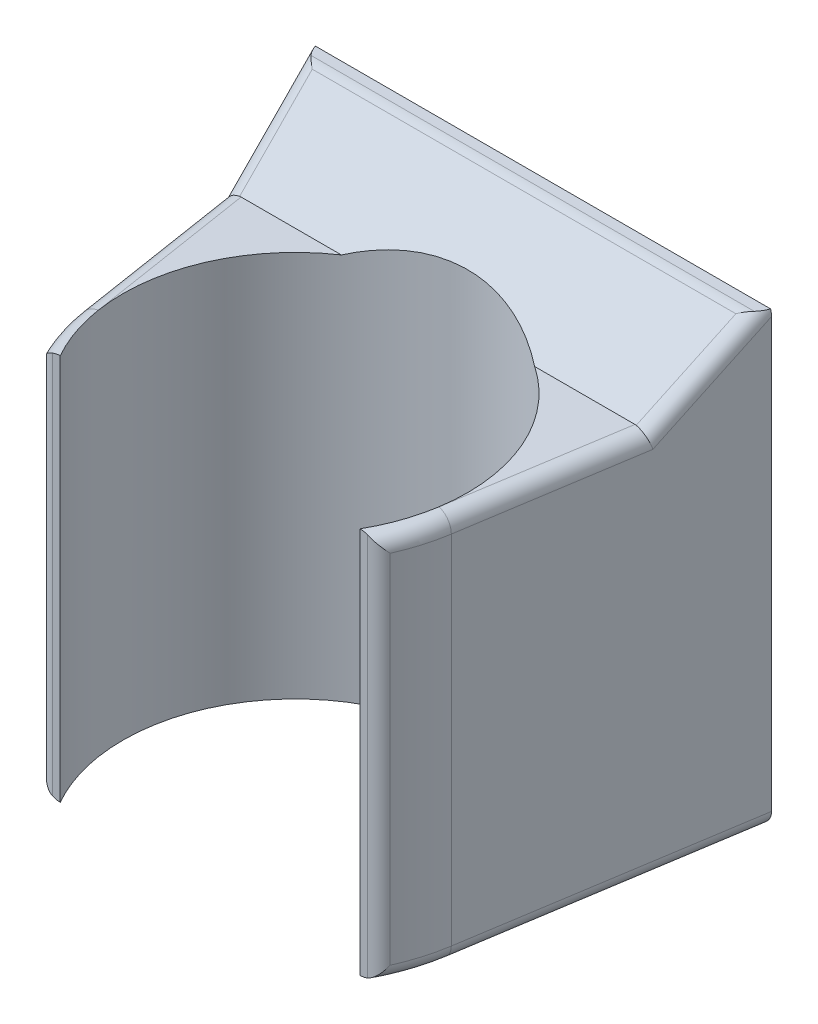
SolidWorks part; units mm, degrees
material "Acrílico (Impacto medio-alto)"
ref_plane "Alzado" through (0, 0, 0) normal (0, 0, 1) x (1, 0, 0)
ref_plane "Planta" through (0, 0, 0) normal (0, 1, 0) x (1, 0, 0)
ref_plane "Vista lateral" through (0, 0, 0) normal (1, 0, 0) x (0, 0, -1)
sketch "Croquis1" plane through (0, 0, 0) normal (0, 1, 0) x (1, 0, 0)
  line L0 (11.1355, -5.6789) -> (-11.1355, -5.6789)
  line L1 (12.3484, -1.9408) -> (15.25, 16.5211)
  line L2 (15.25, 16.5211) -> (-15.25, 16.5211)
  line L3 (-15.25, 16.5211) -> (-12.3484, -1.9408)
  arc A1 (11.1355, -5.6789) -> (12.3484, -1.9408) centre (0, 0) ccw
  arc A4 (-12.3484, -1.9408) -> (-11.1355, -5.6789) centre (0, 0) ccw
  dimension "D1" = 12.5
  dimension "D2" = 11.1355
  dimension "D3" = 12.3484
  dimension "D4" = 15.25
extrude "Saliente-Extruir1" add sketch "Croquis1" along normal blind 30
sketch "Croquis4" plane through (0, 30, 0) normal (0, 1, 0) x (1, 0, 0)
  line L0 (-14.1498, 9.5211) -> (14.1498, 9.5211)
  line L1 (-15.25, 16.5211) -> (-12.3484, -1.9408) construction
  line L2 (12.3484, -1.9408) -> (15.25, 16.5211) construction
  line L3 (15.25, 16.5211) -> (-15.25, 16.5211) construction
  line L8 (-15.25, 16.5211) -> (-12.3484, -1.9408)
  line L9 (-11.1355, -5.6789) -> (11.1355, -5.6789)
  line L10 (12.3484, -1.9408) -> (15.25, 16.5211)
  line L11 (15.25, 16.5211) -> (-15.25, 16.5211)
  line L12 (-14.1498, 9.5211) -> (-12.3484, -1.9408)
  line L13 (-11.1355, -5.6789) -> (11.1355, -5.6789)
  line L14 (12.3484, -1.9408) -> (14.1498, 9.5211)
  arc A2 (-12.3484, -1.9408) -> (-11.1355, -5.6789) centre (0, 0) ccw
  arc A3 (11.1355, -5.6789) -> (12.3484, -1.9408) centre (0, 0) ccw
  arc A4 (-12.3484, -1.9408) -> (-11.1355, -5.6789) centre (0, 0) ccw
  arc A5 (11.1355, -5.6789) -> (12.3484, -1.9408) centre (0, 0) ccw
  dimension "D1" = 7
  dimension "D2" = 0
extrude "Cortar-Extruir1" cut sketch "Croquis4" against normal blind 4.2
chamfer "Chaflán1" distance 6 angle 35 1 edges at (0, 30, -9.5211) first distance on face at (0, 30, -13.0211)
sketch "Croquis5" plane through (0, 30, 0) normal (0, 1, 0) x (1, 0, 0)
  line L0 (-10, -5.6789) -> (10, -5.6789)
  line L1 (-11.1355, -5.6789) -> (11.1355, -5.6789) construction
  line L2 (15.25, 16.5211) -> (-15.25, 16.5211) construction
  circle A1 centre (0, 0) radius 11.5
  point P6 (0, -5.6789)
  point P7 (0, -5.6789)
  point P8 (0, 0)
  point P11 (0, 16.5211)
  point P12 (0, 0)
  dimension "D1" = 23
  dimension "D2" = 20
extrude "Cortar-Extruir2" cut sketch "Croquis5" against normal through all contours L0 A1 region at (0, 30, -2.003)
fillet "Redondeo1" radius 1 13 edges at (11.1355, 12.9, 5.6789) (-11.1355, 12.9, 5.6789) (0, 30, -15.5211) (-11.8898, 0, 3.8578) (-11.8898, 25.8, 3.8578) (11.8898, 0, 3.8578) (11.8898, 25.8, 3.8578) (-13.7992, 0, -7.2902) (-13.2493, 25.8, -3.7911) (13.7992, 0, -7.2902) (13.2493, 25.8, -3.7911) (-14.6215, 27.9, -12.522) (14.6215, 27.9, -12.522)
